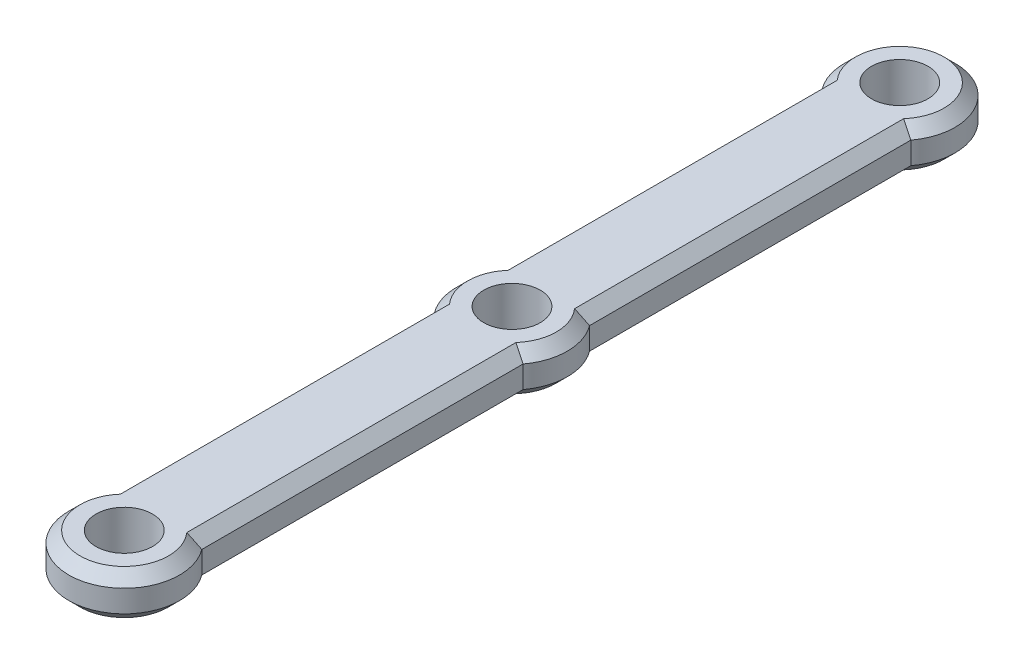
SolidWorks part; units mm, degrees
ref_plane "前视基准面" through (0, 0, 0) normal (0, 0, 1) x (1, 0, 0)
ref_plane "上视基准面" through (0, 0, 0) normal (0, 1, 0) x (1, 0, 0)
ref_plane "右视基准面" through (0, 0, 0) normal (1, 0, 0) x (0, 0, -1)
other "Configuration Table"
sketch "草图1" plane through (0, 0, 0) normal (0, 1, 0) x (1, 0, 0)
  line L0 (0, -35) -> (0, 35) construction
  line L3 (-4, 32) -> (-4, 3)
  line L4 (4, 32) -> (4, 3)
  line L5 (-4, -3) -> (-4, -32)
  line L6 (4, -3) -> (4, -32)
  arc A1 (4, 32) -> (-4, 32) centre (0, 35) ccw
  arc A2 (-4, -32) -> (4, -32) centre (0, -35) ccw
  arc A3 (-4, 3) -> (-4, -3) centre (0, 0) ccw
  arc A4 (4, -3) -> (4, 3) centre (0, 0) ccw
  point P2 (0, 0)
  dimension "D3" = 10
  dimension "D4" = 5
  dimension "D5" = 5
  dimension "D1" = 70
  dimension "D2" = 8
extrude "凸台-拉伸1" add sketch "草图1" along normal blind 4
sketch "草图2" plane through (0, 4, 0) normal (0, 1, 0) x (1, 0, 0)
  line L0 (0, 0) -> (99.318, 0) construction
  circle A0 centre (0, 35) radius 2.55
  circle A1 centre (0, -35) radius 2.55
  circle A2 centre (0, 0) radius 2.55
  dimension "D1" = 5.1
  dimension "D2" = 5.1
extrude "切除-拉伸1" cut sketch "草图2" against normal through all
chamfer "倒角1" distance 1 angle 45 16 edges at (0, 0, -40) (-4, 0, -17.5) (0, 0, 40) (4, 0, -17.5) (0, 4, -40) (-4, 4, -17.5) (0, 4, 40) (4, 4, -17.5) (5, 0, 0) (4, 0, 17.5) (-4, 0, 17.5) (-5, 0, 0) (5, 4, 0) (4, 4, 17.5) (-4, 4, 17.5) (-5, 4, 0)
